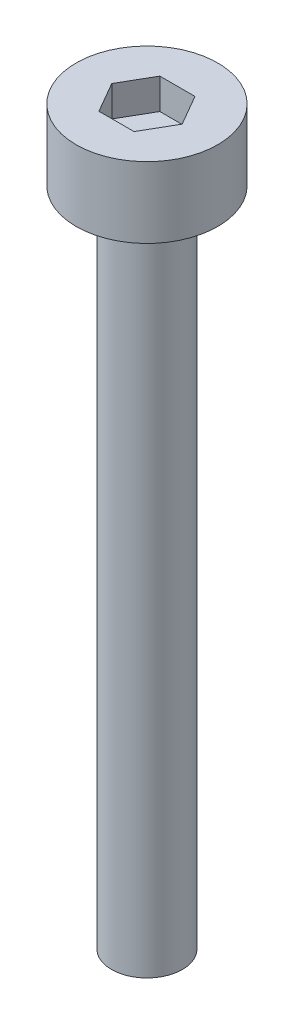
SolidWorks part; units mm, degrees
ref_plane "Front Plane" through (0, 0, 0) normal (0, 0, 1) x (1, 0, 0)
ref_plane "Top Plane" through (0, 0, 0) normal (0, 1, 0) x (1, 0, 0)
ref_plane "Right Plane" through (0, 0, 0) normal (1, 0, 0) x (0, 0, -1)
sketch "Sketch1" plane through (0, 0, 0) normal (0, 1, 0) x (1, 0, 0)
  circle A0 centre (0, 0) radius 1.5
  dimension "D1" = 3
extrude "ScrewShaft" add sketch "Sketch1" along normal blind 28
sketch "Sketch2" plane through (0, 28, 0) normal (0, 1, 0) x (1, 0, 0)
  circle A0 centre (0, 0) radius 3
  dimension "D1" = 6
extrude "Boss-Extrude2" add sketch "Sketch2" along normal blind 3
sketch "Sketch3" plane through (0, 31, 0) normal (0, 1, 0) x (1, 0, 0)
  line L0 (0, 0) -> (0, 1.29) construction
  line L1 (1.4896, 0) -> (0.7448, 1.29)
  line L2 (0.7448, 1.29) -> (-0.7448, 1.29)
  line L3 (-0.7448, 1.29) -> (-1.4896, 0)
  line L4 (-1.4896, 0) -> (-0.7448, -1.29)
  line L5 (-0.7448, -1.29) -> (0.7448, -1.29)
  line L6 (0.7448, -1.29) -> (1.4896, 0)
  circle A0 centre (0, 0) radius 1.29 construction
  dimension "D1" = 2.58
extrude "Cut-Extrude1" cut sketch "Sketch3" against normal blind 1.3
equation "\"X-ROD-SPACING\"=45"
equation "\"Y-ROD-SPACING\"=75"
equation "\"Z-ROD-SPACING\"=17.5"
equation "\"Y-BED-OFFSET\"=2"
equation "\"Y-BED-ROD-INSET\"=3.5"
equation "\"T-SLOT-NUT-FILLET-RADIUS\"=0.25"
equation "\"T-SLOT-SCREW-SHAFT-RADIUS\"=1.75"
equation "\"T-SLOT-SCREW-SHAFT-CUTOUT-LENGTH\"=10.5"
equation "\"T-SLOT-NUT-DEPTH\"=4.2"
equation "\"T-SLOT-NUT-WIDTH\"=3"
equation "\"T-SLOT-NUT-END-DISTANCE\"=8"
equation "\"ACRYLIC-THICKNESS\"=10"
equation "\"ACRYLIC-THICKNESS2\"=4.5"
equation "\"ACRYLIC-TAB-CUTOUT-SIZE\"=\"ACRYLIC-THICKNESS\"+\"ACRYLIC-TAB-TOLERANCE\"*2"
equation "\"ACRYLIC-TAB-WIDTH\"=\"ACRYLIC-THICKNESS\""
equation "\"ACRYLIC-M3-HOLE\"=3.1"
equation "\"SMOOTHROD-CAP-SCREW-DISTANCE\"=20"
equation "\"FRAME-WIDTH-INNER\"=370"
equation "\"NEMA17-HOLE-SPACING\"=31"
equation "\"NEMA17-CENTRAL-CUTOUT\"=22.5"
equation "\"Z-BRACKET-REACH\"=55"
equation "\"TOP-BRACKET-SPACING\"=40"
equation "\"SMOOTHROD-X-LENGTH\"=350"
equation "\"SMOOTHROD-Y-LENGTH\"=350"
equation "\"SMOOTHROD-Z-LENGTH\"=350"
equation "\"SMOOTHROD-TIGHTENING-HEADROOM\"=.25"
equation "\"LEADSCREW-Z-LENGTH\"=300"
equation "\"SCREW-LENGTH-FRAME\"=\"ACRYLIC-THICKNESS\" + 10"
equation "\"SCREW-HEAD-RADIUS\"=6"
equation "\"PRINTED-X-SMOOTHROD-DIAMETER\"=8.2"
equation "\"PRINTED-X-SMOOTHROD-CUTOUT\"=10"
equation "\"PRINTED-X-BASE-HEIGHT\"=10"
equation "\"PRINTED-LM8UU-CUTOUT-SIZE\"=15.25"
equation "\"PRINTED-LM8UU-CUTOUT-LENGTH\"=24.5"
equation "\"PRINTED-X-IDLER-HEIGHT\"=16"
equation "\"PSU-MOUNTING-WIDTH\"=95"
equation "\"PSU-MOUNTING-HEIGHT\"=177"
equation "\"D1@ScrewShaft\"=\"SCREW-LENGTH-EXTRUDER\""
equation "\"D1@Sketch2\"=\"SCREW-HEAD-RADIUS\""
equation "\"Y-BED-SCREW-SPACING\"=209"
equation "\"Y-BED-SCREW-CUTOUT-SLOT-HEIGHT\"=2"
equation "\"Z-ROD-INSET\"=16"
equation "\"SCREW-LENGTH-MOTOR\"=\"ACRYLIC-THICKNESS\" + 5"
equation "\"SCREW-LENGTH-EXTRUDER\"=28"
equation "\"Y-BELT-TO-ROD-DISTANCE\"=20"
equation "\"SPOOL-HOLDER-ROD-SPACING\"=150"
equation "\"ACRYLIC-X-CARRIAGE-WIDTH\"=55"
equation "\"ACRYLIC-X-CARRIAGE-HEIGHT\"=75"
equation "\"ACRYLIC-X-CARRIAGE-CENTER-TAB-SPACING\"=14"
